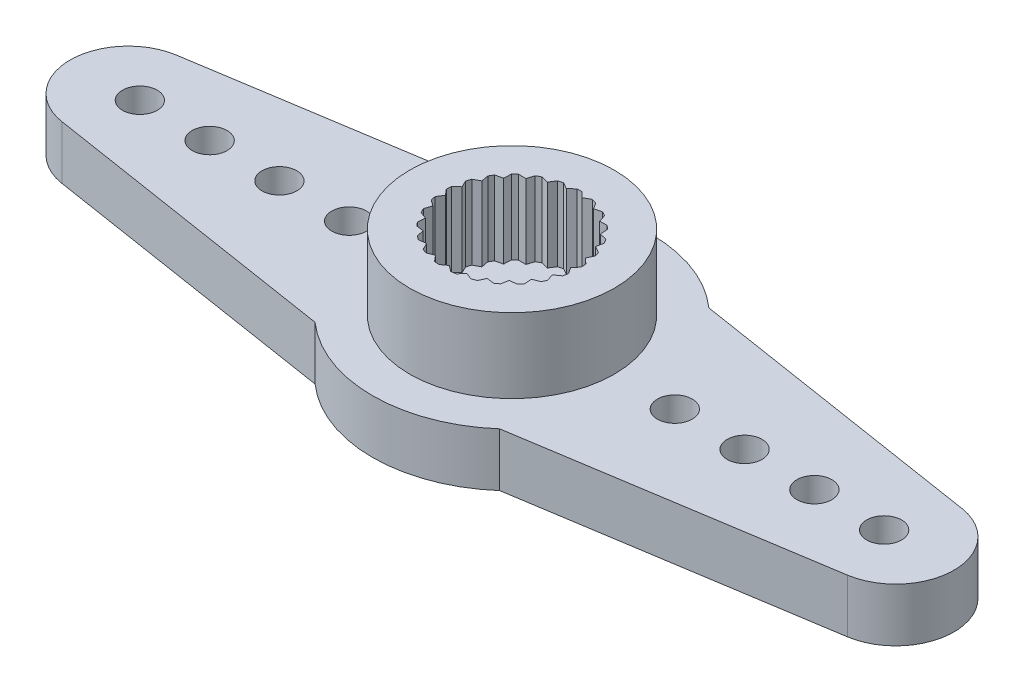
SolidWorks part; units mm, degrees
material "ABS"
ref_plane "Front Plane" through (0, 0, 0) normal (0, 0, 1) x (1, 0, 0)
ref_plane "Top Plane" through (0, 0, 0) normal (0, 1, 0) x (1, 0, 0)
ref_plane "Right Plane" through (0, 0, 0) normal (1, 0, 0) x (0, 0, -1)
sketch "Sketch2" plane through (0, 0, 0) normal (0, 1, 0) x (1, 0, 0)
  circle A0 centre (0, 0) radius 6
  circle A1 centre (0, 0) radius 1.5
  dimension "D1" = 12
  dimension "D2" = 3
extrude "Boss-Extrude1" add sketch "Sketch2" along normal mid plane 2.3
sketch "Sketch3" plane through (0, 1.15, 0) normal (0, 1, 0) x (1, 0, 0)
  line L0 (0, 0) -> (0, 2.9) construction
  line L3 (0, 0) -> (0.376, 2.9763) construction
  line L52 (0.1074, 2.898) -> (0.3384, 2.6787)
  line L53 (-0.1074, 2.898) -> (-0.3384, 2.6787)
  line L54 (0.8248, 2.7802) -> (0.9939, 2.5104)
  line L55 (0.6167, 2.8337) -> (0.3384, 2.6787)
  line L56 (1.4903, 2.4878) -> (1.587, 2.1843)
  line L57 (1.302, 2.5913) -> (0.9939, 2.5104)
  line L58 (2.0621, 2.039) -> (2.0804, 1.721)
  line L59 (1.9055, 2.1861) -> (1.587, 2.1843)
  line L60 (2.5044, 1.4621) -> (2.443, 1.1496)
  line L61 (2.3893, 1.6435) -> (2.0804, 1.721)
  line L62 (2.7894, 0.7934) -> (2.6522, 0.5059)
  line L63 (2.723, 0.9977) -> (2.443, 1.1496)
  line L64 (2.899, 0.0748) -> (2.6947, -0.1695)
  line L65 (2.8855, 0.2892) -> (2.6522, 0.5059)
  line L66 (2.8265, -0.6486) -> (2.5679, -0.8343)
  line L67 (2.8668, -0.4375) -> (2.6947, -0.1695)
  line L68 (2.5765, -1.3311) -> (2.2797, -1.4467)
  line L69 (2.6679, -1.1367) -> (2.5679, -0.8343)
  line L70 (2.1645, -1.93) -> (1.8483, -1.9682)
  line L71 (2.3014, -1.7645) -> (2.2797, -1.4467)
  line L72 (1.6165, -2.4077) -> (1.3007, -2.366)
  line L73 (1.7903, -2.2814) -> (1.8483, -1.9682)
  line L74 (0.967, -2.734) -> (0.6715, -2.6152)
  line L75 (1.1667, -2.655) -> (1.3007, -2.366)
  line L76 (0.2566, -2.8886) -> (0, -2.7)
  line L77 (0.4698, -2.8617) -> (0.6715, -2.6152)
  line L78 (-0.4698, -2.8617) -> (-0.6715, -2.6152)
  line L79 (-0.2566, -2.8886) -> (0, -2.7)
  line L80 (-1.1667, -2.655) -> (-1.3007, -2.366)
  line L81 (-0.967, -2.734) -> (-0.6715, -2.6152)
  line L82 (-1.7903, -2.2814) -> (-1.8483, -1.9682)
  line L83 (-1.6165, -2.4077) -> (-1.3007, -2.366)
  line L84 (-2.3014, -1.7645) -> (-2.2797, -1.4467)
  line L85 (-2.1645, -1.93) -> (-1.8483, -1.9682)
  line L86 (-2.6679, -1.1367) -> (-2.5679, -0.8343)
  line L87 (-2.5765, -1.3311) -> (-2.2797, -1.4467)
  line L88 (-2.8668, -0.4375) -> (-2.6947, -0.1695)
  line L89 (-2.8265, -0.6486) -> (-2.5679, -0.8343)
  line L90 (-2.8855, 0.2892) -> (-2.6522, 0.5059)
  line L91 (-2.899, 0.0748) -> (-2.6947, -0.1695)
  line L92 (-2.723, 0.9977) -> (-2.443, 1.1496)
  line L93 (-2.7894, 0.7934) -> (-2.6522, 0.5059)
  line L94 (-2.3893, 1.6435) -> (-2.0804, 1.721)
  line L95 (-2.5044, 1.4621) -> (-2.443, 1.1496)
  line L96 (-1.9055, 2.1861) -> (-1.587, 2.1843)
  line L97 (-2.0621, 2.039) -> (-2.0804, 1.721)
  line L98 (-1.302, 2.5913) -> (-0.9939, 2.5104)
  line L99 (-1.4903, 2.4878) -> (-1.587, 2.1843)
  line L100 (-0.6167, 2.8337) -> (-0.3384, 2.6787)
  line L101 (-0.8248, 2.7802) -> (-0.9939, 2.5104)
  line L102 (-2.533, 1.6075) -> (-2.3893, 1.6435) construction
  line L103 (-2.533, 1.6075) -> (-2.5044, 1.4621) construction
  line L104 (-2.8532, 0.9271) -> (-2.723, 0.9977) construction
  line L105 (-2.8532, 0.9271) -> (-2.7894, 0.7934) construction
  line L106 (-2.9941, 0.1884) -> (-2.8855, 0.2892) construction
  line L107 (-2.9941, 0.1884) -> (-2.899, 0.0748) construction
  line L108 (-2.9469, -0.5621) -> (-2.8668, -0.4375) construction
  line L109 (-2.9469, -0.5621) -> (-2.8265, -0.6486) construction
  line L110 (0, 3) -> (0.1074, 2.898) construction
  line L111 (0, 2.9) -> (0, 3) construction
  line L112 (0, 3) -> (-0.1074, 2.898) construction
  line L113 (-0.7461, 2.9057) -> (-0.6167, 2.8337) construction
  line L114 (-0.7461, 2.9057) -> (-0.8248, 2.7802) construction
  line L115 (-1.4453, 2.6289) -> (-1.302, 2.5913) construction
  line L116 (-1.4453, 2.6289) -> (-1.4903, 2.4878) construction
  line L117 (-2.0536, 2.1869) -> (-1.9055, 2.1861) construction
  line L118 (-2.0536, 2.1869) -> (-2.0621, 2.039) construction
  line L119 (-2.7145, -1.2773) -> (-2.6679, -1.1367) construction
  line L120 (-2.7145, -1.2773) -> (-2.5765, -1.3311) construction
  line L121 (-2.3115, -1.9123) -> (-2.3014, -1.7645) construction
  line L122 (-2.3115, -1.9123) -> (-2.1645, -1.93) construction
  line L123 (-1.7634, -2.4271) -> (-1.7903, -2.2814) construction
  line L124 (-1.7634, -2.4271) -> (-1.6165, -2.4077) construction
  line L125 (-1.1044, -2.7893) -> (-1.1667, -2.655) construction
  line L126 (-1.1044, -2.7893) -> (-0.967, -2.734) construction
  line L127 (-0.376, -2.9763) -> (-0.4698, -2.8617) construction
  line L128 (-0.376, -2.9763) -> (-0.2566, -2.8886) construction
  line L129 (0.376, -2.9763) -> (0.2566, -2.8886) construction
  line L130 (0.376, -2.9763) -> (0.4698, -2.8617) construction
  line L131 (1.1044, -2.7893) -> (0.967, -2.734) construction
  line L132 (1.1044, -2.7893) -> (1.1667, -2.655) construction
  line L133 (1.7634, -2.4271) -> (1.6165, -2.4077) construction
  line L134 (1.7634, -2.4271) -> (1.7903, -2.2814) construction
  line L135 (2.3115, -1.9123) -> (2.3014, -1.7645) construction
  line L136 (2.3115, -1.9123) -> (2.1645, -1.93) construction
  line L137 (2.7145, -1.2773) -> (2.6679, -1.1367) construction
  line L138 (2.7145, -1.2773) -> (2.5765, -1.3311) construction
  line L139 (2.9469, -0.5621) -> (2.8668, -0.4375) construction
  line L140 (2.9469, -0.5621) -> (2.8265, -0.6486) construction
  line L141 (2.9941, 0.1884) -> (2.8855, 0.2892) construction
  line L142 (2.9941, 0.1884) -> (2.899, 0.0748) construction
  line L143 (2.8532, 0.9271) -> (2.723, 0.9977) construction
  line L144 (2.8532, 0.9271) -> (2.7894, 0.7934) construction
  line L145 (2.533, 1.6075) -> (2.3893, 1.6435) construction
  line L146 (2.533, 1.6075) -> (2.5044, 1.4621) construction
  line L147 (2.0536, 2.1869) -> (1.9055, 2.1861) construction
  line L148 (2.0536, 2.1869) -> (2.0621, 2.039) construction
  line L149 (1.4453, 2.6289) -> (1.302, 2.5913) construction
  line L150 (1.4453, 2.6289) -> (1.4903, 2.4878) construction
  line L151 (0.7461, 2.9057) -> (0.6167, 2.8337) construction
  line L152 (0.7461, 2.9057) -> (0.8248, 2.7802) construction
  circle A0 centre (0, 0) radius 4.4
  circle A1 centre (0, 0) radius 3 construction
  circle A2 centre (0, 0) radius 2.7 construction
  arc A3 (-0.6167, 2.8337) -> (-0.8248, 2.7802) centre (0, 0) ccw
  arc A4 (-0.1074, 2.898) -> (-0.6167, 2.8337) centre (0, 0) ccw construction
  arc A5 (-0.8248, 2.7802) -> (-1.302, 2.5913) centre (0, 0) ccw construction
  arc A6 (-1.302, 2.5913) -> (-1.4903, 2.4878) centre (0, 0) ccw
  arc A7 (-1.4903, 2.4878) -> (-1.9055, 2.1861) centre (0, 0) ccw construction
  arc A8 (-1.9055, 2.1861) -> (-2.0621, 2.039) centre (0, 0) ccw
  arc A9 (-2.0621, 2.039) -> (-2.3893, 1.6435) centre (0, 0) ccw construction
  arc A10 (-2.3893, 1.6435) -> (-2.5044, 1.4621) centre (0, 0) ccw
  arc A11 (-2.5044, 1.4621) -> (-2.723, 0.9977) centre (0, 0) ccw construction
  arc A12 (-2.723, 0.9977) -> (-2.7894, 0.7934) centre (0, 0) ccw
  arc A13 (-2.7894, 0.7934) -> (-2.8855, 0.2892) centre (0, 0) ccw construction
  arc A14 (-2.8855, 0.2892) -> (-2.899, 0.0748) centre (0, 0) ccw
  arc A15 (-2.899, 0.0748) -> (-2.8668, -0.4375) centre (0, 0) ccw construction
  arc A16 (-2.8668, -0.4375) -> (-2.8265, -0.6486) centre (0, 0) ccw
  arc A17 (-2.8265, -0.6486) -> (-2.6679, -1.1367) centre (0, 0) ccw construction
  arc A18 (-2.6679, -1.1367) -> (-2.5765, -1.3311) centre (0, 0) ccw
  arc A19 (-2.5765, -1.3311) -> (-2.3014, -1.7645) centre (0, 0) ccw construction
  arc A20 (-2.3014, -1.7645) -> (-2.1645, -1.93) centre (0, 0) ccw
  arc A21 (-2.1645, -1.93) -> (-1.7903, -2.2814) centre (0, 0) ccw construction
  arc A22 (-1.7903, -2.2814) -> (-1.6165, -2.4077) centre (0, 0) ccw
  arc A23 (-1.6165, -2.4077) -> (-1.1667, -2.655) centre (0, 0) ccw construction
  arc A24 (-1.1667, -2.655) -> (-0.967, -2.734) centre (0, 0) ccw
  arc A25 (-0.967, -2.734) -> (-0.4698, -2.8617) centre (0, 0) ccw construction
  arc A26 (-0.4698, -2.8617) -> (-0.2566, -2.8886) centre (0, 0) ccw
  arc A27 (-0.2566, -2.8886) -> (0.2566, -2.8886) centre (0, 0) ccw construction
  arc A28 (0.2566, -2.8886) -> (0.4698, -2.8617) centre (0, 0) ccw
  arc A29 (0.4698, -2.8617) -> (0.967, -2.734) centre (0, 0) ccw construction
  arc A30 (0.967, -2.734) -> (1.1667, -2.655) centre (0, 0) ccw
  arc A31 (1.1667, -2.655) -> (1.6165, -2.4077) centre (0, 0) ccw construction
  arc A32 (1.6165, -2.4077) -> (1.7903, -2.2814) centre (0, 0) ccw
  arc A33 (1.7903, -2.2814) -> (2.1645, -1.93) centre (0, 0) ccw construction
  arc A34 (2.1645, -1.93) -> (2.3014, -1.7645) centre (0, 0) ccw
  arc A35 (2.3014, -1.7645) -> (2.5765, -1.3311) centre (0, 0) ccw construction
  arc A36 (2.5765, -1.3311) -> (2.6679, -1.1367) centre (0, 0) ccw
  arc A37 (2.6679, -1.1367) -> (2.8265, -0.6486) centre (0, 0) ccw construction
  arc A38 (2.8265, -0.6486) -> (2.8668, -0.4375) centre (0, 0) ccw
  arc A39 (2.8668, -0.4375) -> (2.899, 0.0748) centre (0, 0) ccw construction
  arc A40 (2.899, 0.0748) -> (2.8855, 0.2892) centre (0, 0) ccw
  arc A41 (2.8855, 0.2892) -> (2.7894, 0.7934) centre (0, 0) ccw construction
  arc A42 (2.7894, 0.7934) -> (2.723, 0.9977) centre (0, 0) ccw
  arc A43 (2.723, 0.9977) -> (2.5044, 1.4621) centre (0, 0) ccw construction
  arc A44 (2.5044, 1.4621) -> (2.3893, 1.6435) centre (0, 0) ccw
  arc A45 (2.3893, 1.6435) -> (2.0621, 2.039) centre (0, 0) ccw construction
  arc A46 (2.0621, 2.039) -> (1.9055, 2.1861) centre (0, 0) ccw
  arc A47 (1.9055, 2.1861) -> (1.4903, 2.4878) centre (0, 0) ccw construction
  arc A48 (1.4903, 2.4878) -> (1.302, 2.5913) centre (0, 0) ccw
  arc A49 (1.302, 2.5913) -> (0.8248, 2.7802) centre (0, 0) ccw construction
  arc A50 (0.8248, 2.7802) -> (0.6167, 2.8337) centre (0, 0) ccw
  arc A51 (0.3635, 2.8771) -> (0.1074, 2.898) centre (0, 0) ccw construction
  arc A52 (0.1074, 2.898) -> (-0.1074, 2.898) centre (0, 0) ccw
  arc A53 (0.6167, 2.8337) -> (0.3635, 2.8771) centre (0, 0) ccw construction
  point P84 (0, 0)
  dimension "D1" = 8.8
  dimension "D2" = 5.4
  dimension "D3" = 6
  dimension "D6" = 5.8
  dimension "D4" = 7.2
  dimension "D5" = 25
extrude "Boss-Extrude2" add sketch "Sketch3" along normal blind 3.2
sketch "Sketch4" plane through (0, 0, 0) normal (0, 1, 0) x (1, 0, 0)
  line L0 (0, 0) -> (16, 0) construction
  line L1 (3.9686, 4.5) -> (16.8881, 2.4697)
  line L2 (3.9686, -4.5) -> (16.8881, -2.4697)
  line L3 (16, 0) -> (13, 0) construction
  circle A0 centre (0, 0) radius 6 construction
  arc A1 (3.9686, -4.5) -> (3.9686, 4.5) centre (0, 0) ccw
  arc A2 (16.8881, 2.4697) -> (16.8881, -2.4697) centre (16.5, 0) cw
  circle A3 centre (16, 0) radius 0.75
  circle A4 centre (13, 0) radius 0.75
  circle A5 centre (10, 0) radius 0.75
  circle A6 centre (7, 0) radius 0.75
  dimension "D3" = 2.5
  dimension "D5" = 1.5
  dimension "D2" = 9
  dimension "D7" = 3
  dimension "D4" = 0.5
  dimension "D1" = 16
  dimension "D6" = 4
extrude "Boss-Extrude3" add sketch "Sketch4" along normal mid plane 2.3
pattern_circular "CirPattern1" count 2 over 360 about axis through (0, 4.35, 0) along (0, 1, 0) of "Boss-Extrude3"
sketch "Sketch5" [suppressed] plane through (0, 0, 0) normal (0, 1, 0) x (1, 0, 0)
  line L0 (3, 7) -> (-3, 7) construction
  circle A0 centre (0, 0) radius 10
  circle A1 centre (0, 7) radius 0.75
  circle A2 centre (-3, 7) radius 0.75
  circle A3 centre (3, 7) radius 0.75
  circle A4 centre (7, 3) radius 0.75
  circle A5 centre (7, 0) radius 0.75
  circle A6 centre (7, -3) radius 0.75
  circle A7 centre (3, -7) radius 0.75
  circle A8 centre (0, -7) radius 0.75
  circle A9 centre (-3, -7) radius 0.75
  circle A10 centre (-7, -3) radius 0.75
  circle A11 centre (-7, 0) radius 0.75
  circle A12 centre (-7, 3) radius 0.75
  circle A13 centre (0, 0) radius 1.5 construction
  circle A14 centre (0, 0) radius 1.5
  point P8 (0, 7)
  point P31 (0, 0)
  dimension "D1" = 1.5
  dimension "D3" = 2.25
  dimension "D4" = 6
  dimension "D2" = 7
  dimension "D5" = 4
extrude "Boss-Extrude4" [suppressed] add sketch "Sketch5" along normal mid plane 2.3
sketch "Sketch6" plane through (0, 1.15, 0) normal (0, 1, 0) x (1, 0, 0)
  line L0 (-16.8881, 2.4697) -> (-3.9686, 4.5)
  line L1 (-16.8881, -2.4697) -> (-3.9686, -4.5)
  line L2 (3.9686, 4.5) -> (16.8881, 2.4697)
  line L3 (16.8881, -2.4697) -> (3.9686, -4.5)
  arc A0 (-16.8881, 2.4697) -> (-16.8881, -2.4697) centre (-16.5, 0) ccw
  arc A1 (-3.9686, 4.5) -> (3.9686, 4.5) centre (0, 0) cw
  arc A2 (-3.9686, -4.5) -> (3.9686, -4.5) centre (0, 0) ccw
  arc A3 (16.8881, -2.4697) -> (16.8881, 2.4697) centre (16.5, 0) ccw
equation "\"N_hole\"= 4"
equation "\"N_horn\"= 2"
equation "\"D6@Sketch4\"=\"N_hole\""
equation "\"D1@CirPattern1\"=\"N_horn\""
equation "\"D1@Sketch4\"=(\"N_hole\" - 1) *3 +7"
